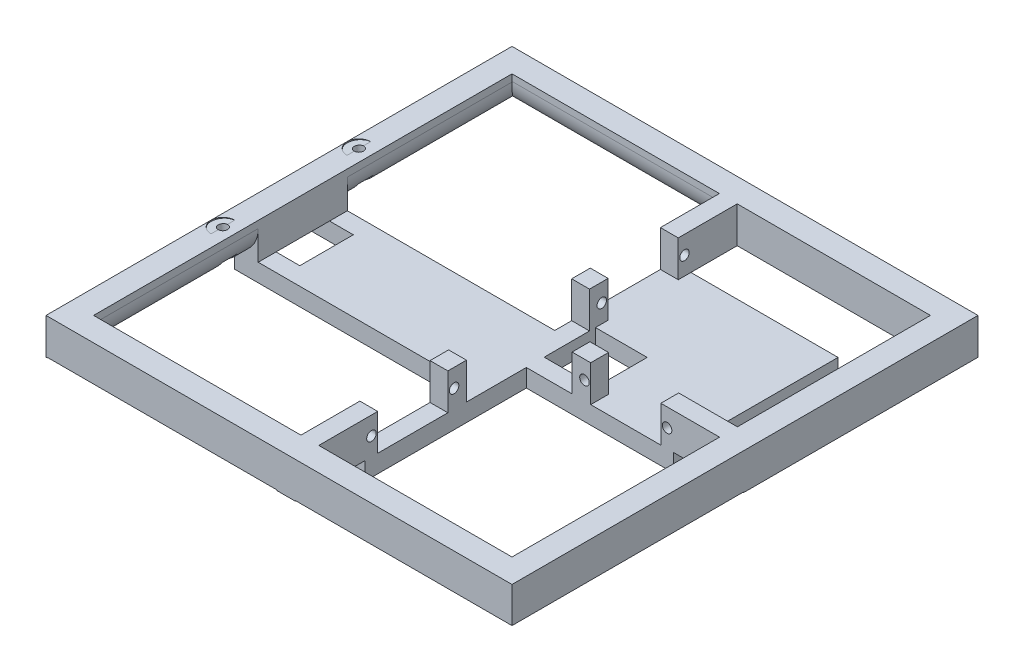
SolidWorks part; units mm, degrees
ref_plane "正面" through (0, 0, 0) normal (0, 0, 1) x (1, 0, 0)
ref_plane "平面" through (0, 0, 0) normal (0, 1, 0) x (1, 0, 0)
ref_plane "右側面" through (0, 0, 0) normal (1, 0, 0) x (0, 0, -1)
sketch "ｽｹｯﾁ1" plane through (0, 0, 0) normal (0, 1, 0) x (1, 0, 0)
  line L1 (-70.375, 70.375) -> (70.375, 70.375)
  line L2 (-70.375, 70.375) -> (-70.375, -70.375)
  line L3 (-70.375, -70.375) -> (70.375, -70.375)
  line L4 (70.375, 70.375) -> (70.375, -70.375)
  line L5 (-70.375, 70.375) -> (70.375, -70.375) construction
  line L6 (-70.375, -70.375) -> (70.375, 70.375) construction
  line L7 (-78.375, 78.375) -> (78.375, 78.375)
  line L8 (-78.375, 78.375) -> (-78.375, -78.375)
  line L9 (-78.375, -78.375) -> (78.375, -78.375)
  line L10 (78.375, 78.375) -> (78.375, -78.375)
  line L11 (-78.375, 78.375) -> (78.375, -78.375) construction
  line L12 (-78.375, -78.375) -> (78.375, 78.375) construction
  point P0 (0, 0)
  point P6 (0, 0)
  dimension "D1" = 140.75
  dimension "D2" = 8
  dimension "D3" = 8
extrude "ﾎﾞｽ - 押し出し1" add sketch "ｽｹｯﾁ1" along normal blind 12.2
ref_plane "平面1" through (70.375, 0, 0) normal (-1, 0, 0) x (0, 0, 1)
sketch "ｽｹｯﾁ2" plane through (70.375, 0, 0) normal (-1, 0, 0) x (0, 0, 1)
  line L1 (0.555, 0) -> (-5.445, 0)
  line L2 (0.555, 0) -> (0.555, 12.2)
  line L3 (0.555, 12.2) -> (-5.445, 12.2)
  line L4 (-5.445, 0) -> (-5.445, 12.2)
  line L5 (78.375, 12.2) -> (-78.375, 12.2) construction
  dimension "D1" = 6
extrude "ﾎﾞｽ - 押し出し2" add sketch "ｽｹｯﾁ2" along normal blind 20.25 separate body
ref_plane "平面2" through (0, 0, 0) normal (0, -1, 0) x (-1, 0, 0)
sketch "ｽｹｯﾁ3" plane through (0, 0, 0) normal (0, -1, 0) x (-1, 0, 0)
  line L0 (-50.125, 5.445) -> (-70.375, 5.445) construction
  line L1 (-50.125, -0.555) -> (-54.875, -0.555)
  line L2 (-50.125, -0.555) -> (-50.125, 5.445)
  line L3 (-50.125, 5.445) -> (-54.875, 5.445)
  line L4 (-54.875, -0.555) -> (-54.875, 5.445)
extrude "ﾎﾞｽ - 押し出し3" add sketch "ｽｹｯﾁ3" along normal blind 6
ref_plane "平面3" through (50.125, 0, 0) normal (-1, 0, 0) x (0, 0, 1)
sketch "ｽｹｯﾁ4" plane through (50.125, 0, 0) normal (-1, 0, 0) x (0, 0, 1)
  line L0 (0.555, -6) -> (-5.445, -6) construction
  line L1 (0.555, -6) -> (-5.445, -6)
  line L2 (0.555, -6) -> (0.555, 0)
  line L3 (0.555, 0) -> (-5.445, 0)
  line L4 (-5.445, -6) -> (-5.445, 0)
  line L5 (-5.445, 12.2) -> (-5.445, -6) construction
  line L6 (0.555, -6) -> (0.555, 12.2) construction
extrude "ﾎﾞｽ - 押し出し4" add sketch "ｽｹｯﾁ4" along normal blind 27.35
ref_plane "平面4" through (0, 0, 0) normal (0, 1, 0) x (1, 0, 0)
sketch "ｽｹｯﾁ6" plane through (0, 0, 0) normal (0, 1, 0) x (1, 0, 0)
  line L0 (22.775, 5.445) -> (50.125, 5.445) construction
  line L1 (22.775, -0.555) -> (27.525, -0.555)
  line L2 (22.775, -0.555) -> (22.775, 5.445)
  line L3 (22.775, 5.445) -> (27.525, 5.445)
  line L4 (27.525, -0.555) -> (27.525, 5.445)
  dimension "D1" = 4.75
extrude "ﾎﾞｽ - 押し出し5" add sketch "ｽｹｯﾁ6" along normal blind 12.2
ref_plane "平面5" through (0, 0, 0.555) normal (0, 0, 1) x (1, 0, 0)
sketch "ｽｹｯﾁ7" plane through (0, 0, 0.555) normal (0, 0, 1) x (1, 0, 0)
  circle A0 centre (52.725, 6.1) radius 1.6
extrude "ｶｯﾄ - 押し出し1" cut sketch "ｽｹｯﾁ7" against normal up to next
sketch "ｽｹｯﾁ8" plane through (0, 0, 0.555) normal (0, 0, 1) x (1, 0, 0)
  circle A0 centre (24.925, 6.1) radius 1.6
extrude "ｶｯﾄ - 押し出し2" cut sketch "ｽｹｯﾁ8" against normal up to next
ref_plane "平面6" through (0, 0, -70.375) normal (0, 0, 1) x (1, 0, 0)
sketch "ｽｹｯﾁ9" plane through (0, 0, -70.375) normal (0, 0, 1) x (1, 0, 0)
  line L0 (-0.625, 12.2) -> (9.675, 12.2) construction
  line L1 (-0.625, 0) -> (5.375, 0)
  line L2 (-0.625, 0) -> (-0.625, 12.2)
  line L3 (-0.625, 12.2) -> (5.375, 12.2)
  line L4 (5.375, 0) -> (5.375, 12.2)
  dimension "D1" = 6
extrude "ﾎﾞｽ - 押し出し6" add sketch "ｽｹｯﾁ9" along normal blind 20.33
ref_plane "平面7" through (0, 0, 70.375) normal (0, 0, -1) x (-1, 0, 0)
sketch "ｽｹｯﾁ10" plane through (0, 0, 70.375) normal (0, 0, -1) x (-1, 0, 0)
  line L0 (0.625, 12.2) -> (-9.675, 12.2) construction
  line L1 (0.625, 0) -> (-5.375, 0)
  line L2 (0.625, 0) -> (0.625, 12.2)
  line L3 (0.625, 12.2) -> (-5.375, 12.2)
  line L4 (-5.375, 0) -> (-5.375, 12.2)
  dimension "D1" = 6
extrude "ﾎﾞｽ - 押し出し7" add sketch "ｽｹｯﾁ10" along normal blind 20.33 separate body
sketch "ｽｹｯﾁ11" plane through (0, 0, 0) normal (0, 1, 0) x (1, 0, 0)
  line L0 (-0.625, 50.045) -> (-0.625, 70.375) construction
  line L1 (5.375, 50.045) -> (-0.625, 50.045)
  line L2 (5.375, 50.045) -> (5.375, 54.8)
  line L3 (5.375, 54.8) -> (-0.625, 54.8)
  line L4 (-0.625, 50.045) -> (-0.625, 54.8)
  line L5 (-0.625, 50.045) -> (-0.625, 70.375) construction
  line L6 (-3.125, 54.8) -> (-0.625, 54.8) construction
extrude "ﾎﾞｽ - 押し出し8" add sketch "ｽｹｯﾁ11" against normal blind 6
sketch "ｽｹｯﾁ12" plane through (0, 0, 0) normal (0, 1, 0) x (1, 0, 0)
  line L1 (5.375, -50.045) -> (-0.625, -50.045)
  line L2 (5.375, -50.045) -> (5.375, -54.8)
  line L3 (5.375, -54.8) -> (-0.625, -54.8)
  line L4 (-0.625, -50.045) -> (-0.625, -54.8)
extrude "ﾎﾞｽ - 押し出し9" add sketch "ｽｹｯﾁ12" against normal blind 6
ref_plane "平面8" through (0, 0, 50.045) normal (0, 0, -1) x (-1, 0, 0)
sketch "ｽｹｯﾁ13" plane through (0, 0, 50.045) normal (0, 0, -1) x (-1, 0, 0)
  line L0 (-5.375, 12.2) -> (-5.375, -6) construction
  line L1 (0.625, -6) -> (-5.375, -6)
  line L2 (0.625, -6) -> (0.625, 0)
  line L3 (0.625, 0) -> (-5.375, 0)
  line L4 (-5.375, -6) -> (-5.375, 0)
  line L5 (-123.8777, 0) -> (69.3068, 0) construction
extrude "ﾎﾞｽ - 押し出し10" add sketch "ｽｹｯﾁ13" along normal up to next
ref_plane "平面9" through (22.775, 0, 0) normal (-1, 0, 0) x (0, 0, 1)
sketch "ｽｹｯﾁ14" plane through (22.775, 0, 0) normal (-1, 0, 0) x (0, 0, 1)
  line L0 (0.555, -6) -> (0.555, 12.2) construction
  line L1 (-5.445, -6) -> (0.555, -6)
  line L2 (-5.445, -6) -> (-5.445, 0)
  line L3 (-5.445, 0) -> (0.555, 0)
  line L4 (0.555, -6) -> (0.555, 0)
  dimension "D1" = 6
extrude "ﾎﾞｽ - 押し出し11" add sketch "ｽｹｯﾁ14" along normal up to next
sketch "ｽｹｯﾁ15" plane through (0, 0, 0) normal (0, 1, 0) x (1, 0, 0)
  line L0 (-0.625, 50.045) -> (-0.625, -50.045) construction
  line L1 (-0.625, 22.7) -> (5.375, 22.7)
  line L2 (-0.625, 22.7) -> (-0.625, 27.45)
  line L3 (-0.625, 27.45) -> (5.375, 27.45)
  line L4 (5.375, 22.7) -> (5.375, 27.45)
  line L5 (-3.125, 22.7) -> (-0.625, 22.7) construction
  line L6 (5.375, 50.045) -> (5.375, 5.445) construction
  dimension "D1" = 4.75
sketch "ｽｹｯﾁ16" plane through (0, 0, 0) normal (0, 1, 0) x (1, 0, 0)
  line L0 (-0.625, 50.045) -> (-0.625, -50.045) construction
  line L1 (-0.625, -22.7) -> (5.375, -22.7)
  line L2 (-0.625, -22.7) -> (-0.625, -27.45)
  line L3 (-0.625, -27.45) -> (5.375, -27.45)
  line L4 (5.375, -22.7) -> (5.375, -27.45)
  line L5 (-3.125, -22.7) -> (-0.625, -22.7) construction
  line L6 (5.375, -0.555) -> (5.375, -50.045) construction
  dimension "D1" = 4.75
extrude "ﾎﾞｽ - 押し出し12" add sketch "ｽｹｯﾁ15" along normal blind 12.2
extrude "ﾎﾞｽ - 押し出し13" add sketch "ｽｹｯﾁ16" along normal blind 12.2
ref_plane "平面10" through (-0.625, 0, 0) normal (-1, 0, 0) x (0, 0, 1)
sketch "ｽｹｯﾁ17" plane through (-0.625, 0, 0) normal (-1, 0, 0) x (0, 0, 1)
  circle A0 centre (-52.65, 6.1) radius 1.6
sketch "ｽｹｯﾁ18" plane through (-0.625, 0, 0) normal (-1, 0, 0) x (0, 0, 1)
  circle A0 centre (52.65, 6.1) radius 1.6
extrude "ｶｯﾄ - 押し出し3" cut sketch "ｽｹｯﾁ18" against normal up to next
sketch "ｽｹｯﾁ19" plane through (-0.625, 0, 0) normal (-1, 0, 0) x (0, 0, 1)
  circle A0 centre (-24.8203, 6.1) radius 1.6
sketch "ｽｹｯﾁ20" plane through (-0.625, 0, 0) normal (-1, 0, 0) x (0, 0, 1)
  circle A0 centre (24.85, 6.1) radius 1.6
extrude "ｶｯﾄ - 押し出し4" cut sketch "ｽｹｯﾁ20" against normal up to next
extrude "ｶｯﾄ - 押し出し5" cut sketch "ｽｹｯﾁ19" against normal up to next
extrude "ｶｯﾄ - 押し出し6" cut sketch "ｽｹｯﾁ17" against normal up to next
ref_plane "平面11" through (0, 12.2, 0) normal (0, 1, 0) x (1, 0, 0)
sketch "ｽｹｯﾁ21" plane through (0, 12.2, 0) normal (0, 1, 0) x (1, 0, 0)
  line L0 (-70.375, 0) -> (-78.375, 0) construction
  line L1 (-70.375, 70.375) -> (-70.375, -70.375) construction
  line L2 (-78.375, 78.375) -> (-78.375, -78.375) construction
  line L3 (-74.375, -78.375) -> (-74.375, 78.375)
  line L4 (78.375, 78.375) -> (-78.375, 78.375) construction
  point P11 (-74.375, 0)
ref_plane "平面12" through (-1.6242, 18.5649, 0) normal (-0.0872, 0.9962, 0) x (0, 0, -1)
sketch "ｽｹｯﾁ22" plane through (-1.6242, 18.5649, 0) normal (-0.0872, 0.9962, 0) x (0, 0, -1)
  line L0 (-78.375, 73.0287) -> (78.375, 73.0287) construction
  line L1 (0, 69.0439) -> (0, 77.0135) construction
  line L2 (0, 77.0135) -> (0, 69.0439) construction
  circle A0 centre (-22.875, 73.0287) radius 3.975
  circle A1 centre (22.875, 73.0287) radius 3.975
  dimension "D1" = 22.875
  dimension "D2" = 7.95
extrude "ｶｯﾄ - 押し出し7" cut sketch "ｽｹｯﾁ22" along normal up to next contours A0 | A1
sketch "ｽｹｯﾁ23" plane through (-1.6242, 18.5649, 0) normal (-0.0872, 0.9962, 0) x (0, 0, -1)
  line L0 (0, 76.8015) -> (0, 69.0439) construction
  line L1 (0, 69.0439) -> (0, 77.0135) construction
  circle A0 centre (-22.875, 73.0287) radius 1.55
  circle A1 centre (22.875, 73.0287) radius 1.55
  dimension "D1" = 3.1
extrude "ｶｯﾄ - 押し出し8" cut sketch "ｽｹｯﾁ23" against normal up to next
ref_plane "平面13" through (-0.927, 10.5953, 0) normal (-0.0872, 0.9962, 0) x (0, 0, -1)
sketch "ｽｹｯﾁ25" plane through (-0.625, 0, 0) normal (-1, 0, 0) x (0, 0, 1)
  line L0 (0, 0) -> (0, -6) construction
  line L1 (-22.7, 0) -> (22.7, 0) construction
  line L2 (-54.8, -6) -> (54.8, -6) construction
  line L4 (-15, 0) -> (15, 0)
  line L5 (-15, 0) -> (-15, -6)
  line L6 (-15, -6) -> (15, -6)
  line L7 (15, 0) -> (15, -6)
  line L8 (-15, 0) -> (15, -6) construction
  line L9 (-15, -6) -> (15, 0) construction
  point P6 (0, -3)
  dimension "D1" = 30
extrude "ﾎﾞｽ - 押し出し14" add sketch "ｽｹｯﾁ25" along normal blind 77.75
ref_plane "平面14" through (-78.375, 0, 0) normal (-1, 0, 0) x (0, 0, 1)
sketch "ｽｹｯﾁ26" plane through (-78.375, 0, 0) normal (-1, 0, 0) x (0, 0, 1)
  line L5 (-15, -6) -> (15, -6) construction
  line L6 (-9, -6) -> (9, -6)
  line L7 (-9, -6) -> (-9, 0)
  line L8 (-9, 0) -> (9, 0)
  line L9 (9, -6) -> (9, 0)
  line L10 (-15, 0) -> (-15, -6) construction
  line L11 (15, -6) -> (15, 0) construction
  dimension "D1" = 6
  dimension "D2" = 6
  dimension "D3" = 6
extrude "ｶｯﾄ - 押し出し10" cut sketch "ｽｹｯﾁ26" against normal blind 16
ref_plane "平面15" through (0, 0, -5.445) normal (0, 0, -1) x (-1, 0, 0)
sketch "ｽｹｯﾁ27" plane through (0, 0, -5.445) normal (0, 0, -1) x (-1, 0, 0)
  line L1 (-54.875, -6) -> (-22.775, -6)
  line L2 (-54.875, -6) -> (-54.875, 0)
  line L3 (-54.875, 0) -> (-22.775, 0)
  line L4 (-22.775, -6) -> (-22.775, 0)
extrude "ﾎﾞｽ - 押し出し18" add sketch "ｽｹｯﾁ27" along normal blind 49.36
ref_plane "平面16" through (5.375, 0, 0) normal (1, 0, 0) x (0, 0, -1)
sketch "ｽｹｯﾁ29" plane through (5.375, 0, 0) normal (1, 0, 0) x (0, 0, -1)
  line L1 (22.7, 0) -> (54.8, 0)
  line L2 (22.7, 0) -> (22.7, -6)
  line L3 (22.7, -6) -> (54.8, -6)
  line L4 (54.8, 0) -> (54.8, -6)
extrude "ﾎﾞｽ - 押し出し19" add sketch "ｽｹｯﾁ29" along normal up to next
fillet "ﾌｨﾚｯﾄ3" radius 10 6 edges at (37.875, 0, 70.375) (-35.5, 0, 70.375) (-35.5, 0, -70.375) (-70.375, 0, 42.6875) (-70.375, 0, -42.6875) (70.375, 0, 35.465)
sketch "ｽｹｯﾁ24" plane through (-0.927, 10.5953, 0) normal (-0.0872, 0.9962, 0) x (0, 0, -1)
  line L0 (0, 77.0135) -> (0, 69.0439) construction
  circle A0 centre (-22.875, 73.0287) radius 3.05
  circle A1 centre (22.875, 73.0287) radius 3.05
  dimension "D1" = 6.1
extrude "ｶｯﾄ - 押し出し9" cut sketch "ｽｹｯﾁ24" against normal up to next
ref_plane "平面17" through (50.125, 0, 0) normal (-1, 0, 0) x (0, 0, 1)
sketch "ｽｹｯﾁ30" plane through (50.125, 0, 0) normal (-1, 0, 0) x (0, 0, 1)
  line L1 (0.555, 0) -> (-5.445, 0)
  line L2 (0.555, 0) -> (0.555, 12.2)
  line L3 (0.555, 12.2) -> (-5.445, 12.2)
  line L4 (-5.445, 0) -> (-5.445, 12.2)
extrude "ｶｯﾄ - 押し出し11" cut sketch "ｽｹｯﾁ30" against normal blind 0.5
ref_plane "平面18" through (27.525, 0, 0) normal (1, 0, 0) x (0, 0, -1)
sketch "ｽｹｯﾁ31" plane through (27.525, 0, 0) normal (1, 0, 0) x (0, 0, -1)
  line L1 (5.445, 0) -> (-0.555, 0)
  line L2 (5.445, 0) -> (5.445, 12.2)
  line L3 (5.445, 12.2) -> (-0.555, 12.2)
  line L4 (-0.555, 0) -> (-0.555, 12.2)
extrude "ｶｯﾄ - 押し出し12" cut sketch "ｽｹｯﾁ31" against normal blind 0.5
ref_plane "平面19" through (0, 0, 27.45) normal (0, 0, 1) x (1, 0, 0)
sketch "ｽｹｯﾁ32" plane through (0, 0, 27.45) normal (0, 0, 1) x (1, 0, 0)
  line L1 (-0.625, 0) -> (5.375, 0)
  line L2 (-0.625, 0) -> (-0.625, 12.2)
  line L3 (-0.625, 12.2) -> (5.375, 12.2)
  line L4 (5.375, 0) -> (5.375, 12.2)
extrude "ｶｯﾄ - 押し出し13" cut sketch "ｽｹｯﾁ32" against normal blind 0.5
ref_plane "平面20" through (0, 0, 50.045) normal (0, 0, -1) x (-1, 0, 0)
sketch "ｽｹｯﾁ33" plane through (0, 0, 50.045) normal (0, 0, -1) x (-1, 0, 0)
  line L1 (0.625, 12.2) -> (-5.375, 12.2)
  line L2 (0.625, 12.2) -> (0.625, 0)
  line L3 (0.625, 0) -> (-5.375, 0)
  line L4 (-5.375, 12.2) -> (-5.375, 0)
extrude "ｶｯﾄ - 押し出し14" cut sketch "ｽｹｯﾁ33" against normal blind 0.5
ref_plane "平面21" through (0, 0, -27.45) normal (0, 0, -1) x (-1, 0, 0)
sketch "ｽｹｯﾁ34" plane through (0, 0, -27.45) normal (0, 0, -1) x (-1, 0, 0)
  line L1 (0.625, 12.2) -> (-5.375, 12.2)
  line L2 (0.625, 12.2) -> (0.625, 0)
  line L3 (0.625, 0) -> (-5.375, 0)
  line L4 (-5.375, 12.2) -> (-5.375, 0)
extrude "ｶｯﾄ - 押し出し15" cut sketch "ｽｹｯﾁ34" against normal blind 0.5
ref_plane "平面22" through (0, 0, -50.045) normal (0, 0, 1) x (1, 0, 0)
sketch "ｽｹｯﾁ35" plane through (0, 0, -50.045) normal (0, 0, 1) x (1, 0, 0)
  line L1 (-0.625, 0) -> (5.375, 0)
  line L2 (-0.625, 0) -> (-0.625, 12.2)
  line L3 (-0.625, 12.2) -> (5.375, 12.2)
  line L4 (5.375, 0) -> (5.375, 12.2)
extrude "ｶｯﾄ - 押し出し16" cut sketch "ｽｹｯﾁ35" against normal blind 0.5
ref_plane "平面23" through (0, 0, 22.7) normal (0, 0, -1) x (-1, 0, 0)
sketch "ｽｹｯﾁ36" plane through (0, 0, 22.7) normal (0, 0, -1) x (-1, 0, 0)
  line L1 (0.625, 12.2) -> (-5.375, 12.2)
  line L2 (0.625, 12.2) -> (0.625, 0)
  line L3 (0.625, 0) -> (-5.375, 0)
  line L4 (-5.375, 12.2) -> (-5.375, 0)
extrude "ﾎﾞｽ - 押し出し20" add sketch "ｽｹｯﾁ36" along normal blind 2
ref_plane "平面24" through (0, 0, -22.7) normal (0, 0, 1) x (1, 0, 0)
sketch "ｽｹｯﾁ37" plane through (0, 0, -22.7) normal (0, 0, 1) x (1, 0, 0)
  line L1 (-0.625, 0) -> (5.375, 0)
  line L2 (-0.625, 0) -> (-0.625, 12.2)
  line L3 (-0.625, 12.2) -> (5.375, 12.2)
  line L4 (5.375, 0) -> (5.375, 12.2)
extrude "ﾎﾞｽ - 押し出し21" add sketch "ｽｹｯﾁ37" along normal blind 2
ref_plane "平面25" through (22.775, 0, 0) normal (-1, 0, 0) x (0, 0, 1)
sketch "ｽｹｯﾁ38" plane through (22.775, 0, 0) normal (-1, 0, 0) x (0, 0, 1)
  line L1 (-5.445, 0) -> (0.555, 0)
  line L2 (-5.445, 0) -> (-5.445, 12.2)
  line L3 (-5.445, 12.2) -> (0.555, 12.2)
  line L4 (0.555, 0) -> (0.555, 12.2)
extrude "ﾎﾞｽ - 押し出し22" add sketch "ｽｹｯﾁ38" along normal blind 2
